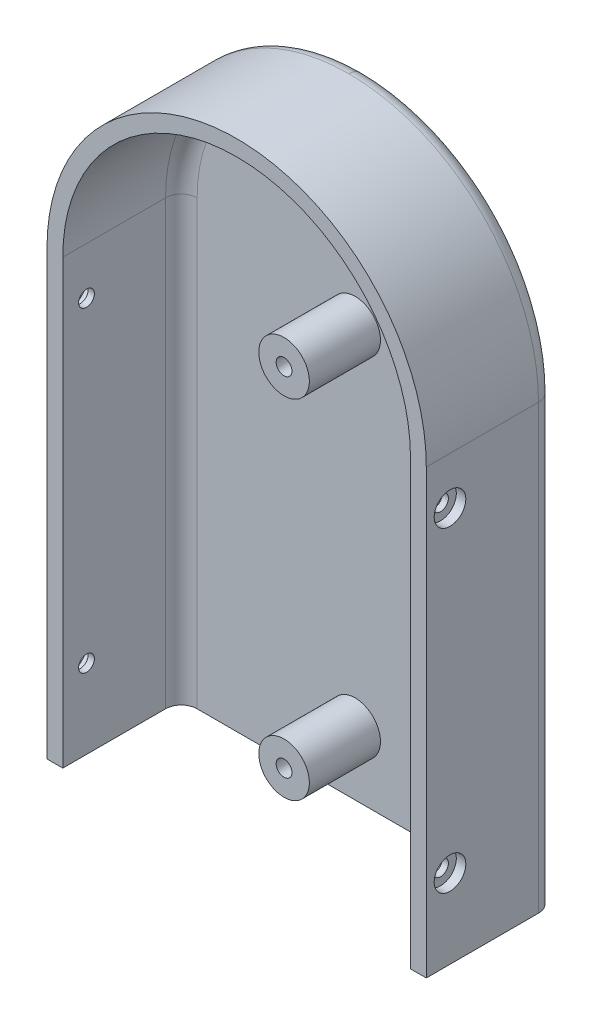
SolidWorks part; units mm, degrees
ref_plane "Front Plane" through (0, 0, 0) normal (0, 0, 1) x (1, 0, 0)
ref_plane "Top Plane" through (0, 0, 0) normal (0, 1, 0) x (1, 0, 0)
ref_plane "Right Plane" through (0, 0, 0) normal (1, 0, 0) x (0, 0, -1)
sketch "Sketch1" plane through (0, 0, 0) normal (0, 0, 1) x (1, 0, 0)
  line L1 (60, -100) -> (-60, -100)
  line L2 (60, -100) -> (60, 100)
  line L3 (60, 100) -> (-60, 100)
  line L4 (-60, -100) -> (-60, 100)
  line L5 (60, -100) -> (-60, 100) construction
  line L6 (60, 100) -> (-60, -100) construction
  point P0 (0, 0)
  dimension "D1" = 120
  dimension "D2" = 200
extrude "Boss-Extrude1" add sketch "Sketch1" along normal blind 3
fillet "Fillet1" radius 60 2 edges at (60, 100, 1.5) (-60, 100, 1.5)
sketch "Sketch4" plane through (0, 0, 3) normal (0, 0, 1) x (1, 0, 0)
  line L3 (55, -100) -> (55, 40)
  line L4 (-55, 40) -> (-55, -100)
  line L5 (-55, -100) -> (-60, -100)
  line L6 (60, -100) -> (60, 40)
  line L7 (-60, 40) -> (-60, -100)
  line L8 (-60, -100) -> (60, -100)
  line L9 (60, -100) -> (60, 40)
  line L10 (-60, 40) -> (-60, -100)
  line L12 (55, -100) -> (60, -100)
  arc A2 (55, 40) -> (0, 95) centre (0, 40) ccw
  arc A3 (0, 95) -> (-55, 40) centre (0, 40) ccw
  arc A4 (60, 40) -> (0, 100) centre (0, 40) ccw
  arc A5 (0, 100) -> (-60, 40) centre (0, 40) ccw
  arc A6 (60, 40) -> (0, 100) centre (0, 40) ccw
  arc A7 (0, 100) -> (-60, 40) centre (0, 40) ccw
  dimension "D1" = 0
  dimension "D2" = 5
extrude "Boss-Extrude2" add sketch "Sketch4" along normal blind 37.5
fillet "Fillet2" radius 5 5 edges at (0, 95, 3) (55, -30, 3) (-55, -30, 3) (-60, -30, 0) (60, -30, 0)
sketch "Sketch6" plane through (60, 0, 0) normal (1, 0, 0) x (0, 0, -1)
  line L0 (-40.5, -100) -> (-40.5, 40) construction
  line L1 (-40.5, -100) -> (-5, -100) construction
  circle A0 centre (-33, -75) radius 2.5
  circle A1 centre (-33, 25) radius 2.5
  dimension "D1" = 7.5
  dimension "D2" = 25
  dimension "D3" = 100
extrude "Cut-Extrude1" cut sketch "Sketch6" against normal blind 37.5
sketch "Sketch7" plane through (60, 0, 0) normal (1, 0, 0) x (0, 0, -1)
  circle A0 centre (-33, 25) radius 5
  circle A1 centre (-33, -75) radius 5
extrude "Cut-Extrude2" cut sketch "Sketch7" against normal blind 3
mirror "Mirror1" about plane through (0, 0, 0) normal (1, 0, 0) of "Cut-Extrude2", "Cut-Extrude1"
sketch "Sketch9" plane through (0, 0, 3) normal (0, 0, 1) x (1, 0, 0)
  circle A0 centre (0, 30) radius 8
  circle A1 centre (0, 30) radius 2.5
  dimension "D1" = 5
  dimension "D2" = 30
extrude "Boss-Extrude3" add sketch "Sketch9" along normal blind 22.5
sketch "Sketch10" plane through (0, 0, 3) normal (0, 0, 1) x (1, 0, 0)
  circle A0 centre (0, 30) radius 6
extrude "Cut-Extrude3" cut sketch "Sketch10" against normal blind 3
pattern_linear "LPattern1" count 2 spacing 110 along (0, -1, 0) of "Boss-Extrude3", "Cut-Extrude3"
